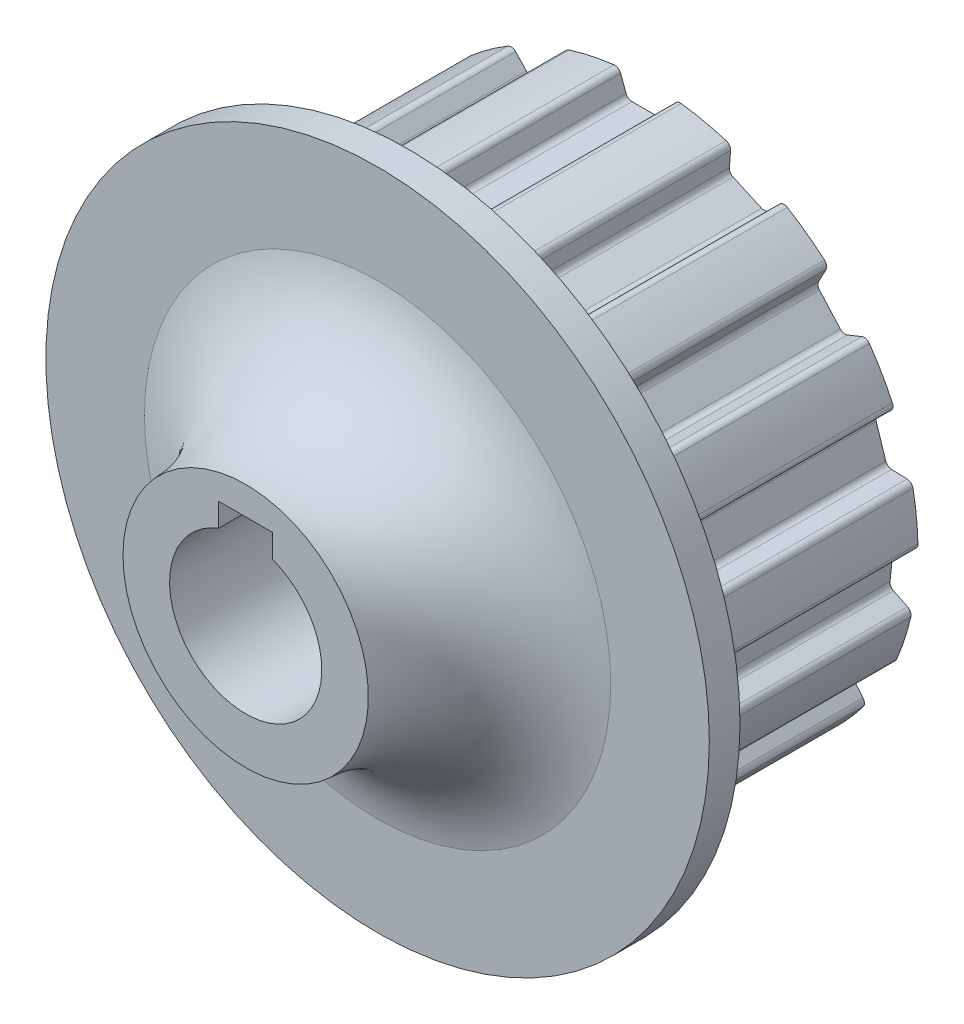
SolidWorks part; units mm, degrees
ref_plane "Front Plane" through (0, 0, 0) normal (0, 0, 1) x (1, 0, 0)
ref_plane "Top Plane" through (0, 0, 0) normal (0, 1, 0) x (1, 0, 0)
ref_plane "Right Plane" through (0, 0, 0) normal (1, 0, 0) x (0, 0, -1)
sketch "Sketch1" plane through (0, 0, 0) normal (0, 1, 0) x (1, 0, 0)
  line L0 (0, 36.1296) -> (0, -19.4741) construction
sketch "Sketch7" plane through (0, 0, 0) normal (0, 0, 1) x (1, 0, 0)
  line L0 (0, 0) -> (0, 20.9536) construction
  line L1 (-2.325, 21.9086) -> (-2.9401, 23.5986) construction
  line L2 (-2.325, 21.9086) -> (-1.6298, 19.9986) construction
  line L3 (-1.6298, 19.9986) -> (1.6298, 19.9986) construction
  line L4 (1.6298, 19.9986) -> (2.325, 21.9086) construction
  line L5 (2.325, 21.9086) -> (-2.325, 21.9086) construction
  line L6 (0, 19.9986) -> (0, 21.9086) construction
  line L7 (2.325, 21.9086) -> (2.9401, 23.5986) construction
  line L8 (-2.9401, 23.5986) -> (2.9401, 23.5986) construction
  line L9 (0, 0) -> (8.5226, 19.1421) construction
  line L10 (8.5226, 19.1421) -> (8.9611, 20.1269) construction
  line L11 (0, 21.9086) -> (0, 22.0316) construction
  line L12 (0, 22.0316) -> (0, 23.7811) construction
  line L13 (0, 22.9064) -> (9.3169, 20.926) construction
  line L14 (8.9611, 20.1269) -> (9.6726, 21.7251) construction
  circle A1 centre (0, 0) radius 20.9536 construction
  circle A2 centre (-1.2727, 20.5086) radius 0.51 construction
  circle A3 centre (1.2727, 20.5086) radius 0.51 construction
  circle A4 centre (0, 0) radius 22.0316
  circle A5 centre (0, 0) radius 23.7811 construction
  dimension "D3" = 40
  dimension "D6" = 1.02
  dimension "D1" = 3.6
  dimension "D2" = 24
  dimension "D7" = 9.525
  dimension "D4" = 1.91
  dimension "D5" = 4.65
extrude "Boss-Extrude1" add sketch "Sketch7" along normal blind 7.25 and the other way blind 7.25 contours A4 region at (0, 0, 0)
sketch "Sketch14" plane through (0, 0, 0) normal (1, 0, 0) x (0, 0, -1)
  line L0 (-18, 0) -> (-18, 10)
  line L1 (-18, 0) -> (0, 0)
  line L2 (0, 0) -> (0, 19)
  line L3 (0, 19) -> (-7.25, 19)
  line L4 (-7.25, 19) -> (-18, 10)
  line L5 (-7.25, 22.0316) -> (-7.25, -22.0316) construction
  line L6 (-18, 6.7395) -> (-3.3555, 19) construction
  arc A0 (-7.25, 19) -> (-18, 10) centre (-18.1316, 21.0773) cw
  dimension "D1" = 10
  dimension "D2" = 19
  dimension "D3" = 18
  dimension "D4" = 2.5
revolve "Revolve1" add sketch "Sketch14" angle 360 about L0 region at (0, 7.5733, 7.5341) region at (0, 9.2725, 16.1663) region at (0, 17.2765, 6.6188)
sketch "Sketch9" plane through (0, 0, 0) normal (0, 0, 1) x (1, 0, 0)
  line L0 (2, 0) -> (-2, 0) construction
  line L1 (-2, 0) -> (-2, 7.5) construction
  line L2 (-2, 7.5) -> (2, 7.5) construction
  line L3 (2, 7.5) -> (2, 0) construction
  circle A0 centre (0, 0) radius 6 construction
  dimension "D1" = 12
  dimension "D2" = 4
  dimension "D3" = 7.5
sketch "Sketch10" plane through (0, 0, 0) normal (0, 0, 1) x (1, 0, 0)
  line L0 (2, 0) -> (-2, 0) construction
  line L1 (-2.2, 7.7) -> (2.2, 7.7)
  line L2 (-2.2, 7.7) -> (-2.2, 0)
  line L3 (-2.2, 0) -> (2.2, 0)
  line L4 (2.2, 7.7) -> (2.2, 0)
  line L5 (-2, 7.5) -> (2, 7.5) construction
  line L6 (2, 7.5) -> (2, 0) construction
  circle A0 centre (0, 0) radius 6.2
  circle A1 centre (0, 0) radius 6 construction
  dimension "D1" = 0.2
  dimension "D2" = 0.2
  dimension "D3" = 0.2
extrude "Cut-Extrude3" cut sketch "Sketch10" against normal through all both and the other way through all contours A0 L4 L1 L2 | L2 A0 L4 L3 | L4 A0 L2 L3 region at (0, 6.8793, 0) region at (0, 3.0348, 0) region at (0, -0.8613, 0)
sketch "Sketch11" plane through (0, 0, 0) normal (0, 1, 0) x (1, 0, 0)
  line L0 (22.0316, 7.25) -> (-22.0316, 7.25) construction
  line L1 (11, 7.25) -> (17.5, 7.25)
  line L2 (11, 7.25) -> (11, 4.75)
  line L3 (11, 4.75) -> (17.5, 4.75)
  line L4 (17.5, 7.25) -> (17.5, 4.75)
  line L5 (-22.0316, -7.25) -> (22.0316, -7.25) construction
  line L6 (11, -7.25) -> (17.5, -7.25)
  line L7 (11, -7.25) -> (11, -4.75)
  line L8 (11, -4.75) -> (17.5, -4.75)
  line L9 (17.5, -7.25) -> (17.5, -4.75)
  line L11 (11, 4.75) -> (11, -4.75) construction
  line L12 (17.5, -4.75) -> (17.5, 4.75) construction
  line L13 (6.2, 7.25) -> (-6.2, 7.25) construction
  line L14 (0, 7.25) -> (22.5, 7.25)
  line L15 (0, 7.25) -> (0, -7.25)
  line L16 (0, -7.25) -> (22.5, -7.25)
  line L17 (22.5, 7.25) -> (22.5, -7.25)
  line L18 (-6.2, -7.25) -> (6.2, -7.25) construction
  line L19 (6, 7.25) -> (6, -7.25) construction
  dimension "D1" = 22.5
  dimension "D2" = 6
  dimension "D3" = 5
  dimension "D4" = 5
  dimension "D5" = 2.5
revolve "Cut-Revolve1" [suppressed] cut sketch "Sketch11" angle 360 about L0
sketch "Sketch15" plane through (0, 0, -7.25) normal (0, 0, -1) x (-1, 0, 0)
  circle A0 centre (0, 0) radius 8.0081
  circle A1 centre (0, 0) radius 2.25
  dimension "D1" = 4.5
extrude "Boss-Extrude2" add sketch "Sketch15" against normal blind 5.5
sketch "Sketch16" plane through (0, 0, -7.25) normal (0, 0, -1) x (-1, 0, 0)
  circle A0 centre (0, 0) radius 5
  dimension "D1" = 10
extrude "Cut-Extrude4" cut sketch "Sketch16" against normal blind 3
sketch "Sketch17" plane through (0, 0, -7.25) normal (0, 0, -1) x (-1, 0, 0)
  circle A0 centre (0, 0) radius 22.0316
  circle A1 centre (0, 0) radius 22.0316 construction
  circle A2 centre (0, 0) radius 5
  circle A3 centre (0, 0) radius 5 construction
extrude "Boss-Extrude3" add sketch "Sketch17" along normal blind 7.5
sketch "Sketch8" plane through (0, 0, 0) normal (0, 0, 1) x (1, 0, 0)
  line L6 (-1.6298, 19.9986) -> (-2.3698, 22.0316)
  line L7 (-2.3698, 22.0316) -> (2.3698, 22.0316)
  line L8 (2.3698, 22.0316) -> (1.6298, 19.9986)
  line L9 (1.6298, 19.9986) -> (-1.6298, 19.9986)
  line L10 (-2.325, 21.9086) -> (-1.6298, 19.9986) construction
  line L11 (1.6298, 19.9986) -> (2.325, 21.9086) construction
  line L12 (6.6453, 18.9326) -> (6.7962, 21.0908)
  line L13 (6.7962, 21.0908) -> (11.126, 19.163)
  line L14 (11.126, 19.163) -> (9.6231, 17.6067)
  line L15 (9.6231, 17.6067) -> (6.6453, 18.9326)
  line L16 (13.7713, 14.5929) -> (14.787, 16.5031)
  line L17 (14.787, 16.5031) -> (17.9584, 12.981)
  line L18 (17.9584, 12.981) -> (15.9524, 12.1705)
  line L19 (15.9524, 12.1705) -> (13.7713, 14.5929)
  line L20 (18.5162, 7.73) -> (20.221, 9.0619)
  line L21 (20.221, 9.0619) -> (21.6856, 4.5544)
  line L22 (21.6856, 4.5544) -> (19.5235, 4.6299)
  line L23 (19.5235, 4.6299) -> (18.5162, 7.73)
  line L24 (20.0594, -0.4695) -> (22.1587, 0.0539)
  line L25 (22.1587, 0.0539) -> (21.6632, -4.6597)
  line L26 (21.6632, -4.6597) -> (19.7187, -3.7113)
  line L27 (19.7187, -3.7113) -> (20.0594, -0.4695)
  line L28 (18.1342, -8.5879) -> (20.2649, -8.9635)
  line L29 (20.2649, -8.9635) -> (17.8951, -13.0681)
  line L30 (17.8951, -13.0681) -> (16.5044, -11.4108)
  line L31 (16.5044, -11.4108) -> (18.1342, -8.5879)
  line L32 (13.0734, -15.2212) -> (14.8671, -16.4311)
  line L33 (14.8671, -16.4311) -> (11.0327, -19.2169)
  line L34 (11.0327, -19.2169) -> (10.4363, -17.1372)
  line L35 (10.4363, -17.1372) -> (13.0734, -15.2212)
  line L36 (5.7521, -19.2227) -> (6.8986, -21.0575)
  line L37 (6.8986, -21.0575) -> (2.2626, -22.0429)
  line L38 (2.2626, -22.0429) -> (2.5637, -19.9005)
  line L39 (2.5637, -19.9005) -> (5.7521, -19.2227)
  line L40 (-2.5637, -19.9005) -> (-2.2626, -22.0429)
  line L41 (-2.2626, -22.0429) -> (-6.8986, -21.0575)
  line L42 (-6.8986, -21.0575) -> (-5.7521, -19.2227)
  line L43 (-5.7521, -19.2227) -> (-2.5637, -19.9005)
  line L44 (-10.4363, -17.1372) -> (-11.0327, -19.2169)
  line L45 (-11.0327, -19.2169) -> (-14.8671, -16.4311)
  line L46 (-14.8671, -16.4311) -> (-13.0734, -15.2212)
  line L47 (-13.0734, -15.2212) -> (-10.4363, -17.1372)
  line L48 (-16.5044, -11.4108) -> (-17.8951, -13.0681)
  line L49 (-17.8951, -13.0681) -> (-20.2649, -8.9635)
  line L50 (-20.2649, -8.9635) -> (-18.1342, -8.5879)
  line L51 (-18.1342, -8.5879) -> (-16.5044, -11.4108)
  line L52 (-19.7187, -3.7113) -> (-21.6632, -4.6597)
  line L53 (-21.6632, -4.6597) -> (-22.1587, 0.0539)
  line L54 (-22.1587, 0.0539) -> (-20.0594, -0.4695)
  line L55 (-20.0594, -0.4695) -> (-19.7187, -3.7113)
  line L56 (-19.5235, 4.6299) -> (-21.6856, 4.5544)
  line L57 (-21.6856, 4.5544) -> (-20.221, 9.0619)
  line L58 (-20.221, 9.0619) -> (-18.5162, 7.73)
  line L59 (-18.5162, 7.73) -> (-19.5235, 4.6299)
  line L60 (-15.9524, 12.1705) -> (-17.9584, 12.981)
  line L61 (-17.9584, 12.981) -> (-14.787, 16.5031)
  line L62 (-14.787, 16.5031) -> (-13.7713, 14.5929)
  line L63 (-13.7713, 14.5929) -> (-15.9524, 12.1705)
  line L64 (-9.6231, 17.6067) -> (-11.126, 19.163)
  line L65 (-11.126, 19.163) -> (-6.7962, 21.0908)
  line L66 (-6.7962, 21.0908) -> (-6.6453, 18.9326)
  line L67 (-6.6453, 18.9326) -> (-9.6231, 17.6067)
  circle A0 centre (0, 0) radius 22.0316 construction
  point P119 (0, 0)
  dimension "D1" = 15
extrude "Cut-Extrude2" cut sketch "Sketch8" against normal through all both and the other way through all
fillet "Fillet2" radius 0.51 60 edges at (-6.787, 20.9602, -3.75) (-11.035, 19.0689, -3.75) (-14.7256, 16.3875, -3.75) (-17.837, 12.9319, -3.75) (-20.1179, 8.9813, -3.75) (-21.5548, 4.5589, -3.75) (-22.0316, 0.0222, -3.75) (-21.5456, -4.6023, -3.75) (-20.1359, -8.9408, -3.75) (-17.8109, -12.9678, -3.75) (-14.7585, -16.3578, -3.75) (-10.9966, -19.0911, -3.75) (-6.8293, -20.9465, -3.75) (-2.2809, -21.9133, -3.75) (2.2809, -21.9133, -3.75) (6.8293, -20.9465, -3.75) (10.9966, -19.0911, -3.75) (14.7585, -16.3578, -3.75) (17.8109, -12.9678, -3.75) (20.1359, -8.9408, -3.75) (21.5456, -4.6023, -3.75) (22.0316, 0.0222, -3.75) (21.5548, 4.5589, -3.75) (20.1179, 8.9813, -3.75) (17.837, 12.9319, -3.75) (14.7256, 16.3875, -3.75) (11.035, 19.0689, -3.75) (6.787, 20.9602, -3.75) (2.325, 21.9086, -3.75) (-6.6453, 18.9326, -3.75) (-9.6231, 17.6067, -3.75) (-13.7713, 14.5929, -3.75) (-15.9524, 12.1705, -3.75) (-18.5162, 7.73, -3.75) (-19.5235, 4.6299, -3.75) (-20.0594, -0.4695, -3.75) (-19.7187, -3.7113, -3.75) (-18.1342, -8.5879, -3.75) (-16.5044, -11.4108, -3.75) (-13.0734, -15.2212, -3.75) (-10.4363, -17.1372, -3.75) (-5.7521, -19.2227, -3.75) (-2.5637, -19.9005, -3.75) (2.5637, -19.9005, -3.75) (5.7521, -19.2227, -3.75) (10.4363, -17.1372, -3.75) (13.0734, -15.2212, -3.75) (16.5044, -11.4108, -3.75) (18.1342, -8.5879, -3.75) (19.7187, -3.7113, -3.75) (20.0594, -0.4695, -3.75) (19.5235, 4.6299, -3.75) (18.5162, 7.73, -3.75) (15.9524, 12.1705, -3.75) (13.7713, 14.5929, -3.75) (9.6231, 17.6067, -3.75) (6.6453, 18.9326, -3.75) (1.6298, 19.9986, -3.75) (-1.6298, 19.9986, -3.75) (-2.325, 21.9086, -3.75)
sketch "Sketch18" plane through (0, 0, -14.75) normal (0, 0, -1) x (-1, 0, 0)
  circle A0 centre (0, 0) radius 5
  circle A1 centre (0, 0) radius 27.0316
  circle A2 centre (0, 0) radius 22.0316
  circle A3 centre (0, 0) radius 5 construction
  arc A4 (-2.7297, 21.8619) -> (-6.3983, 21.0821) centre (0, 0) ccw construction
  dimension "D1" = 5
extrude "Boss-Extrude4" add sketch "Sketch18" along normal blind 2.5 contours A1 A2 | A2 A0 region at (26.2671, 0, -14.75) region at (21.4085, 0, -14.75)
sketch "Sketch19" plane through (0, 0, 7.25) normal (0, 0, 1) x (1, 0, 0)
  circle A0 centre (0, 0) radius 19
  circle A1 centre (0, 0) radius 27.0316
  circle A2 centre (0, 0) radius 27.0316 construction
  circle A3 centre (0, 0) radius 19 construction
extrude "Boss-Extrude5" add sketch "Sketch19" against normal blind 2.5
fillet "Fillet3" [suppressed] radius 0.5
sketch "Sketch20" plane through (0, 0, 18) normal (0, 0, 1) x (1, 0, 0)
  line L0 (-2.2, 5.7966) -> (-2.2, 7.7)
  line L1 (-2.2, 7.7) -> (2.2, 7.7)
  line L2 (-2.2, 7.7) -> (2.2, 7.7) construction
  line L3 (2.2, 7.7) -> (2.2, 5.7966)
  circle A0 centre (0, 0) radius 6.2
  arc A1 (-2.2, 5.7966) -> (2.2, 5.7966) centre (0, 0) ccw construction
  arc M2 (2.2, 5.7966) -> (-2.2, 5.7966) centre (0, 0) cw
  line M3 (-2.2, 5.7966) -> (-2.2, 7.7)
  line M4 (-2.2, 7.7) -> (2.2, 7.7)
  line M5 (2.2, 7.7) -> (2.2, 5.7966)
extrude "Cut-Extrude5" cut sketch "Sketch20" against normal through all contours A0 M5 M4 M3 | A0 M2 region at (0, 6.8793, 18) region at (0, 0, 18)
ref_plane "Plane1" through (0, 0, -5.25) normal (0, 0, 1) x (1, 0, 0)
sketch "Sketch21" plane through (0, 0, -5.25) normal (0, 0, 1) x (1, 0, 0)
  circle A0 centre (0, 0) radius 8.0081
  circle A1 centre (0, 0) radius 2.25
  circle A2 centre (0, 0) radius 6.2
  arc A3 (-2.2, 5.7966) -> (2.2, 5.7966) centre (0, 0) ccw construction
  dimension "D1" = 4.5
extrude "Boss-Extrude6" add sketch "Sketch21" against normal blind 2.5 contours A2 A1 | A0 A2 region at (-7.7816, 0, -5.25) region at (-6.0246, 0, -5.25)
extrude "Boss-Extrude7" add sketch "Sketch21<4>" against normal up to surface (12 mm away) contours A0 A2 region at (-7.7816, 0, -5.25) up to face at (0, 3.7491, -17.25)
sketch "Sketch21<4>" plane through (0, 0, -5.25) normal (0, 0, 1) x (1, 0, 0) same geometry as "Sketch21"
sketch "Sketch22" plane through (0, 0, 0) normal (0, 1, 0) x (1, 0, 0)
  line L0 (-27.0316, 17.25) -> (-27.0316, 14.75) construction
  line L1 (-27.0316, 17.25) -> (27.0316, 17.25)
  line L2 (-27.0316, 17.25) -> (-27.0316, 14.75)
  line L3 (-27.0316, 14.75) -> (27.0316, 14.75)
  line L4 (27.0316, 17.25) -> (27.0316, 14.75)
  line L5 (-27.0316, 17.25) -> (27.0316, 14.75) construction
  line L6 (-27.0316, 14.75) -> (27.0316, 17.25) construction
  line L7 (-10, -18) -> (10, -18) construction
  line L8 (-27.0316, 14.75) -> (27.0316, 14.75)
  line L9 (-27.0316, 14.75) -> (-27.0316, -18)
  line L10 (-27.0316, -18) -> (27.0316, -18)
  line L11 (27.0316, 14.75) -> (27.0316, -18)
  point P0 (0, 16)
extrude "Cut-Extrude6" cut sketch "Sketch22" against normal through all both and the other way through all contours L4 L1 L2 L3 region at (0, 0, -16)
sketch "Sketch23" plane through (0, 0, -14.75) normal (0, 0, -1) x (-1, 0, 0)
  line L0 (0, 19.9986) -> (0, 6.2) construction
  line L1 (1.2727, 19.9986) -> (-1.2727, 19.9986) construction
  circle A0 centre (0, 0) radius 13.0993 construction
  circle A1 centre (0, 0) radius 6.2 construction
  circle A2 centre (0, -13.0993) radius 1.75
  circle A3 centre (-11.3443, 6.5497) radius 1.75
  circle A4 centre (11.3443, 6.5497) radius 1.75
  point P10 (0, 13.0993)
  point P19 (0, 0)
  point P26 (0, 0)
  dimension "D1" = 3.5
  dimension "D2" = 3
extrude "Cut-Extrude7" cut sketch "Sketch23" against normal blind 6
ref_plane "Plane2" through (0, 0, -12.25) normal (0, 0, -1) x (-1, 0, 0)
sketch "Sketch24" plane through (0, 0, -12.25) normal (0, 0, -1) x (-1, 0, 0)
  line L0 (-19.08, 11.0158) -> (-14.2443, 8.224) construction
  line L1 (-11.3443, 3.201) -> (-8.4443, 4.8753)
  line L2 (-8.4443, 4.8753) -> (-8.4443, 8.224)
  line L3 (-8.4443, 8.224) -> (-11.3443, 9.8983)
  line L4 (-11.3443, 9.8983) -> (-14.2443, 8.224)
  line L5 (-14.2443, 8.224) -> (-14.2443, 4.8753)
  line L6 (-14.2443, 4.8753) -> (-11.3443, 3.201)
  line L7 (2.9, -14.7736) -> (2.9, -11.425)
  line L8 (2.9, -11.425) -> (0, -9.7507)
  line L9 (0, -9.7507) -> (-2.9, -11.425)
  line L10 (-2.9, -11.425) -> (-2.9, -14.7736)
  line L11 (-2.9, -14.7736) -> (0, -16.4479)
  line L12 (0, -16.4479) -> (2.9, -14.7736)
  line L13 (11.3443, 3.201) -> (14.2443, 4.8753)
  line L14 (14.2443, 4.8753) -> (14.2443, 8.224)
  line L15 (14.2443, 8.224) -> (11.3443, 9.8983)
  line L16 (11.3443, 9.8983) -> (8.4443, 8.224)
  line L17 (8.4443, 8.224) -> (8.4443, 4.8753)
  line L18 (8.4443, 4.8753) -> (11.3443, 3.201)
  line L19 (-11.3443, 6.5497) -> (-14.2443, 8.224) construction
  line L20 (11.3443, 6.5497) -> (14.2443, 8.224) construction
  line L21 (19.08, 11.0158) -> (14.2443, 8.224) construction
  line L22 (0, -22.0316) -> (0, -16.4479) construction
  circle A0 centre (-11.3443, 6.5497) radius 2.9 construction
  circle A1 centre (0, -13.0993) radius 2.9 construction
  circle A2 centre (11.3443, 6.5497) radius 2.9 construction
  arc A3 (-18.0731, 12.5999) -> (-19.9484, 9.3518) centre (0, 0) ccw construction
  arc A5 (19.9484, 9.3518) -> (18.0731, 12.5999) centre (0, 0) ccw construction
  arc A6 (-1.8753, -21.9517) -> (1.8753, -21.9517) centre (0, 0) ccw construction
  dimension "D1" = 5.8
extrude "Cut-Extrude8" cut sketch "Sketch24" against normal blind 3
sketch "Sketch25" plane through (0, 0, -9.25) normal (0, 0, -1) x (-1, 0, 0)
  circle A0 centre (0, -13.0993) radius 1.75
  circle A1 centre (-11.3443, 6.5497) radius 1.75
  circle A2 centre (11.3443, 6.5497) radius 1.75
  circle A4 centre (0, -13.0993) radius 1.75 construction
extrude "Boss-Extrude8" add sketch "Sketch25" against normal blind 0.2
